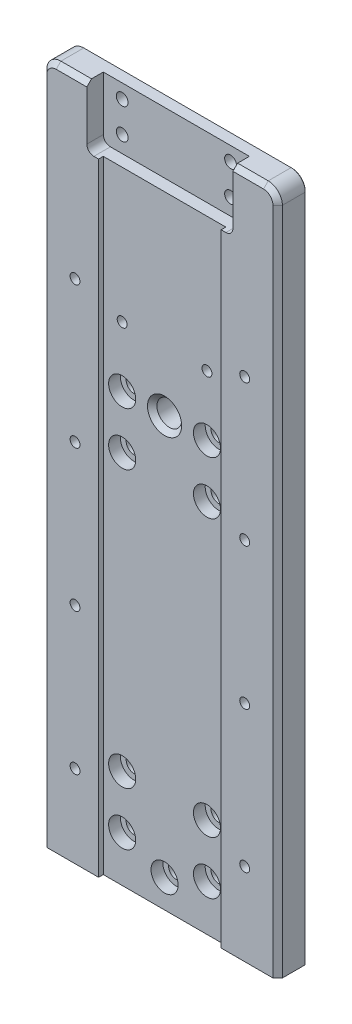
SolidWorks part; units mm, degrees
material "1060 Alloy"
ref_plane "Front Plane" through (0, 0, 0) normal (0, 0, 1) x (1, 0, 0)
ref_plane "Top Plane" through (0, 0, 0) normal (0, 1, 0) x (1, 0, 0)
ref_plane "Right Plane" through (0, 0, 0) normal (1, 0, 0) x (0, 0, -1)
sketch "Sketch1" plane through (0, 0, 0) normal (0, 0, 1) x (1, 0, 0)
  line L1 (50, -145) -> (-50, -145)
  line L2 (50, -145) -> (50, 145)
  line L3 (50, 145) -> (-50, 145)
  line L4 (-50, -145) -> (-50, 145)
  line L5 (50, -145) -> (-50, 145) construction
  line L6 (50, 145) -> (-50, -145) construction
  point P0 (0, 0)
  dimension "D1" = 100
  dimension "D2" = 290
extrude "Boss-Extrude1" add sketch "Sketch1" along normal mid plane 12
sketch "Sketch2" plane through (0, 0, 6) normal (0, 0, 1) x (1, 0, 0)
  line L0 (0, 132) -> (0, 0) construction
  line L1 (31, 119) -> (-31, 119)
  line L2 (31, 119) -> (31, 145)
  line L3 (31, 145) -> (-31, 145)
  line L4 (-31, 119) -> (-31, 145)
  line L5 (31, 119) -> (-31, 145) construction
  line L6 (31, 145) -> (-31, 119) construction
  line L7 (50, 145) -> (-50, 145) construction
  point P0 (0, 132)
  dimension "D1" = 62
  dimension "D2" = 26
extrude "Cut-Extrude1" cut sketch "Sketch2" against normal blind 7
sketch "Sketch3" plane through (0, 0, 6) normal (0, 0, 1) x (1, 0, 0)
  line L0 (-50, -145) -> (50, -145) construction
  line L1 (26, 145) -> (-26, 145)
  line L2 (26, 145) -> (26, -145)
  line L3 (26, -145) -> (-26, -145)
  line L4 (-26, 145) -> (-26, -145)
  line L5 (26, 145) -> (-26, -145) construction
  line L6 (26, -145) -> (-26, 145) construction
  point P0 (0, 0)
  dimension "D1" = 52
extrude "Cut-Extrude2" cut sketch "Sketch3" against normal blind 2
sketch "Sketch4" plane through (0, 0, -6) normal (0, 0, 1) x (1, 0, 0)
  line L0 (0, 132.5) -> (0, 0) construction
  line L1 (23, 126) -> (-23, 126) construction
  line L2 (23, 126) -> (23, 139) construction
  line L3 (23, 139) -> (-23, 139) construction
  line L4 (-23, 126) -> (-23, 139) construction
  line L5 (23, 126) -> (-23, 139) construction
  line L6 (23, 139) -> (-23, 126) construction
  line L7 (31, 145) -> (-31, 145) construction
  line L8 (-18, 62.14) -> (-18, 14.14) construction
  line L9 (-36, 145) -> (-36, -110) construction
  line L10 (-31, 145) -> (-50, 145) construction
  line L11 (-50, -145) -> (-26, -145) construction
  line L12 (0, 0) -> (0, -145) construction
  line L13 (-26, -145) -> (26, -145) construction
  line L14 (50, 2.14) -> (-50, 2.14) construction
  line L15 (18, -103) -> (-18, -103) construction
  line L16 (18, -103) -> (18, -125.5) construction
  line L17 (18, -125.5) -> (-18, -125.5) construction
  line L18 (-18, -103) -> (-18, -125.5) construction
  line L19 (18, -103) -> (-18, -125.5) construction
  line L20 (18, -125.5) -> (-18, -103) construction
  line L21 (50, 2.14) -> (50, 52.14) construction
  line L22 (50, 52.14) -> (-50, 52.14) construction
  line L23 (-50, 2.14) -> (-50, 52.14) construction
  line L24 (50, 2.14) -> (-50, 52.14) construction
  line L25 (50, 52.14) -> (-50, 2.14) construction
  circle A0 centre (-23, 139) radius 2.5
  circle A1 centre (23, 139) radius 2.5
  circle A2 centre (23, 126) radius 2.5
  circle A3 centre (-23, 126) radius 2.5
  circle A4 centre (0, 36.64) radius 5.25
  circle A5 centre (-18, 62.14) radius 2.1
  circle A6 centre (-18, 36.64) radius 3.3
  circle A7 centre (-18, 14.14) radius 3.3
  circle A9 centre (-36, 70) radius 2.1
  circle A10 centre (-36, 58.75) radius 2.1 construction
  circle A11 centre (-36, 10) radius 2.1
  circle A12 centre (-36, -110) radius 2.1
  circle A13 centre (-36, -50) radius 2.1
  circle A14 centre (-18, -103) radius 3.3
  circle A15 centre (-18, -125.5) radius 3.3
  circle A16 centre (18, -103) radius 3.3
  circle A17 centre (18, -125.5) radius 3.3
  circle A18 centre (0, -133) radius 3.3
  circle A20 centre (36, 70) radius 2.1
  circle A21 centre (36, 58.75) radius 2.1 construction
  circle A22 centre (18, 62.14) radius 2.1
  circle A23 centre (18, 14.14) radius 3.3
  circle A24 centre (18, 36.64) radius 3.3
  circle A25 centre (36, 10) radius 2.1
  circle A26 centre (36, -50) radius 2.1
  circle A27 centre (36, -110) radius 2.1
  point P0 (0, 132.5)
  point P36 (0, -114.25)
  point P68 (0, 27.14)
  dimension "D1" = 5
  dimension "D5" = 10.5
  dimension "D12" = 4.2
  dimension "D19" = 6.6
  dimension "D9" = 6.6
  dimension "D2" = 13
  dimension "D3" = 46
  dimension "D4" = 6
  dimension "D8" = 18
  dimension "D10" = 22.5
  dimension "D11" = 36
  dimension "D13" = 35
  dimension "D14" = 60
  dimension "D15" = 60
  dimension "D16" = 48.75
  dimension "D17" = 11.25
  dimension "D20" = 12
  dimension "D21" = 36
  dimension "D23" = 22.5
  dimension "D24" = 100
  dimension "D25" = 50
  dimension "D7" = 10
  dimension "D6" = 12
  dimension "D18" = 147.14
  dimension "D22" = 7.5
extrude "Cut-Extrude HOLES" cut sketch "Sketch4" along normal blind 21
fillet "Fillet1" radius 3 2 edges at (31, 119, 2.5) (-31, 119, 2.5)
fillet "Fillet2" radius 6 2 edges at (50, 145, 0) (-50, 145, 0)
chamfer "Chamfer1" distance 2 angle 45 6 edges at (50, -3, 6) (48.2426, 143.2426, 6) (37.5, 145, 6) (-50, -3, 6) (-48.2426, 143.2426, 6) (-37.5, 145, 6)
sketch "Sketch5" plane through (0, 0, 4) normal (0, 0, 1) x (1, 0, 0)
  circle A1 centre (-18, 36.64) radius 5.75
  circle A2 centre (-18, 14.14) radius 5.75
  circle A3 centre (18, 14.14) radius 5.75
  circle A4 centre (18, 36.64) radius 5.75
  circle A6 centre (18, -103) radius 5.75
  circle A7 centre (-18, -103) radius 5.75
  circle A8 centre (-18, -125.5) radius 5.75
  circle A9 centre (0, -133) radius 5.75
  circle A10 centre (18, -125.5) radius 5.75
  dimension "D1" = 11.5
extrude "Cut-Extrude5" cut sketch "Sketch5" against normal blind 5
chamfer "Chamfer2" distance 2 angle 45 1 edges at (-5.25, 36.64, 4)
chamfer "Chamfer3" distance 0.3 angle 45 5 edges at (-50, -3, -6) (-48.2426, 143.2426, -6) (48.2426, 143.2426, -6) (50, -3, -6) (0, 145, -6)
equation "\"M5_tap\"=4.2mm       ' Below you can do mesurements as follows: cm, mm, ft, in, m, "
equation "\"M5_clearence\"=5.5mm"
equation "\"M6_tap\"=5mm"
equation "\"M6_clearence\"=6.6mm"
equation "\"D1@Sketch4\"=\"M6_tap\""
equation "\"D12@Sketch4\"=\"M5_tap\""
equation "\"D19@Sketch4\"=\"M6_clearence\""
equation "\"work_area_width\"=1100mm"
equation "\"work_area_depth\"=900mm"
equation "\"steel_base_width\"=80mm"
equation "\"steel_base_height\"=50mm"
equation "\"steel_base_wall_thickness\"=3mm"
equation "\"steel_base_radius\"=6mm"
equation "\"steel_sides_width\"=80mm    'this tube is rotated so flip width/height"
equation "\"steel_sides_height\"=50mm    'this tube is rotated so flip width/height"
equation "\"steel_sides_wall_thickness\"=3mm"
equation "\"steel_sides_radius\"=6mm"
equation "\"steel_gantry_width\"=80mm    'this tube is rotated so flip width/height"
equation "\"steel_gantry_height\"=50mm    'this tube is rotated so flip width/height"
equation "\"steel_gantry_wall_thickness\"=3mm"
equation "\"steel_gantry_radius\"=6mm"
equation "\"steel_rollers_width\"=80mm"
equation "\"steel_rollers_height\"=50mm    'keep as low as possible as this increases how big plastic parts are"
equation "\"steel_rollers_wall_thickness\"=3mm"
equation "\"steel_rollers_radius\"=6mm"
equation "\"steel_zbox_width\"=80mm     'if the gantry height (rotated) is too thick, a wider zbox is necessary"
equation "\"steel_zbox_height\"=50mm    'hole patteren changes as the zbox and gantry height (rotated) changes."
equation "\"steel_zbox_wall_thickness\"=3mm"
equation "\"steel_zbox_radius\"=6mm"
equation "\"alu_zangle_width\"=80mm     'check that it doesn't interfer with the gantry"
equation "\"alu_zangle_height\"=50mm"
equation "\"alu_zangle_wall_thickness\"=7mm  'check that it doesn't interfer with the gantry"
equation "\"D9@Sketch4\"=\"M6_clearence\""
equation "\"D25@Sketch4\"=\"steel_zbox_height\""
equation "\"D6@Sketch4\"=\"steel_zbox_radius\"*2"
equation "\"D18@Sketch4\"=\"steel_gantry_width\" + \"alu_zangle_wall_thickness\" + 60.14"
equation "\"D20@Sketch4\"=\"alu_zangle_wall_thickness\" + 5"
